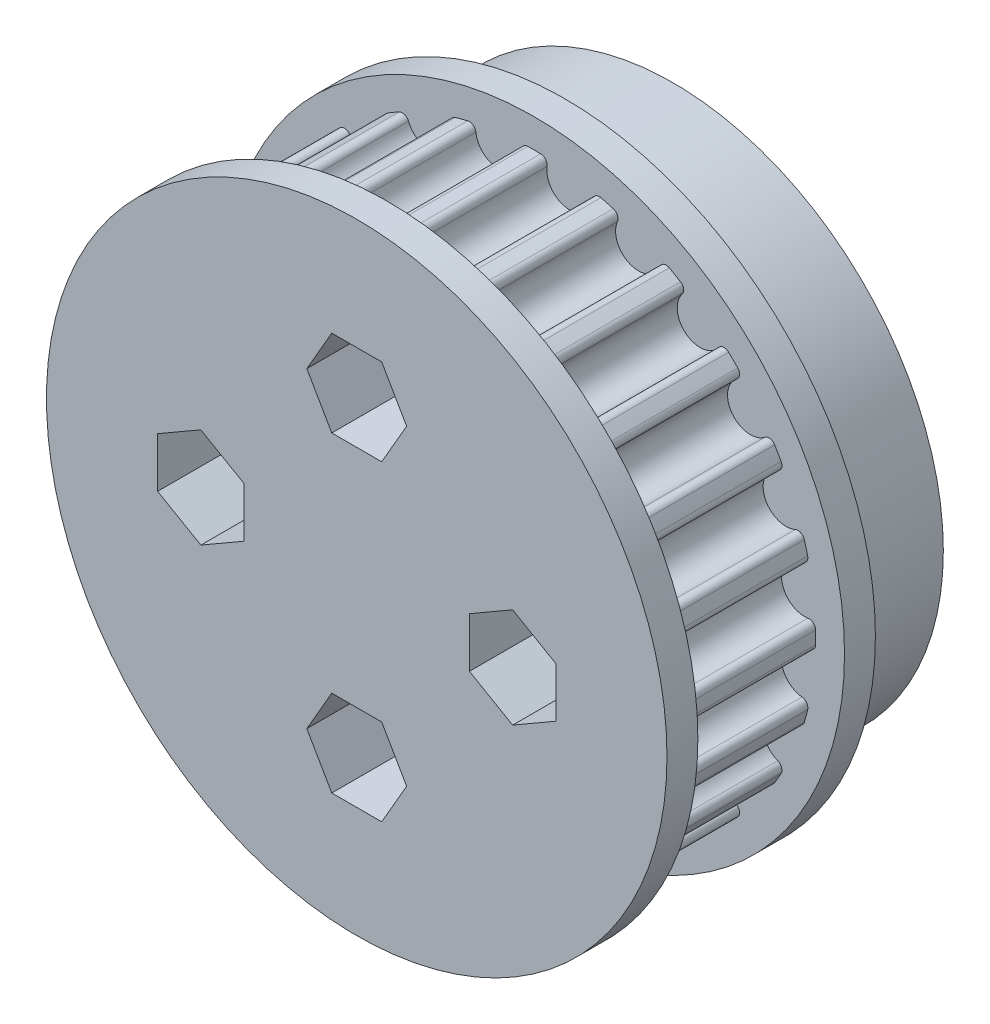
SolidWorks part; units mm, degrees
ref_plane "Front Plane" through (0, 0, 0) normal (0, 0, 1) x (1, 0, 0)
ref_plane "Top Plane" through (0, 0, 0) normal (0, 1, 0) x (1, 0, 0)
ref_plane "Right Plane" through (0, 0, 0) normal (1, 0, 0) x (0, 0, -1)
sketch "Sketch1" plane through (0, 0, 0) normal (0, 0, 1) x (1, 0, 0)
  circle A0 centre (0, 0) radius 19.0986
  dimension "D1" = 38.1972
extrude "Boss-Extrude1" add sketch "Sketch1" along normal mid plane 9.5
sketch "Sketch2" plane through (0, 0, 4.75) normal (0, 0, 1) x (1, 0, 0)
  line L0 (0, 0) -> (2.4929, 18.9352) construction
  line L1 (0, 0) -> (0, 18.2286) construction
  line L2 (0, 18.2286) -> (0, 19.0986)
  line L3 (4.7179, 17.6075) -> (4.9431, 18.4478)
  arc A0 (0, 18.2286) -> (0.4162, 18.2238) centre (0, 0) cw
  arc A1 (0.4162, 18.2238) -> (0.8316, 17.7298) centre (0.4064, 17.794) cw
  arc A2 (0.8316, 17.7298) -> (3.7856, 17.3409) centre (2.3049, 17.5075) ccw
  circle A3 centre (0, 0) radius 19.0986 construction
  arc A4 (4.7179, 17.6075) -> (4.3146, 17.7106) centre (0, 0) ccw
  arc A5 (4.3146, 17.7106) -> (3.7856, 17.3409) centre (4.2129, 17.2928) ccw
  arc A6 (4.9431, 18.4478) -> (0, 19.0986) centre (0, 0) ccw
  point P31 (2.1104, 16.0303)
  circle M1 centre (0, 0) radius 19.0986
  dimension "D1" = 1.49
  dimension "D2" = 0.43
  dimension "D3" = 0.87
  dimension "D5" = 7.5
  dimension "D4" = 2.93
extrude "Cut-Extrude1" cut sketch "Sketch2" against normal through all contours A5 A4 L3 L2 A0 A1 A2 M1 region at (2.3372, 17.7528, 4.75)
pattern_circular "CirPattern1" count 24 over 360 about axis through (0, 0, 4.75) along (0, 0, -1) of "Cut-Extrude1"
sketch "Sketch3" plane through (0, 0, 4.75) normal (0, 0, 1) x (1, 0, 0)
  circle A0 centre (0, 0) radius 20.0986
  dimension "D1" = 40.1972
extrude "Boss-Extrude2" add sketch "Sketch3" along normal blind 2
mirror "Mirror1" about plane through (0, 0, 0) normal (0, 0, 1) of "Boss-Extrude2"
sketch "Sketch5" plane through (0, 0, -6.75) normal (0, 0, 1) x (1, 0, 0)
  circle A0 centre (0, 0) radius 17.5 construction
  circle A1 centre (0, 0) radius 17.5 construction
  circle A2 centre (0, 0) radius 17.5
  dimension "D1" = 0
extrude "Boss-Extrude3" add sketch "Sketch5" against normal up to surface (7 mm away)
sketch "Sketch4" plane through (0, 0, 6.75) normal (0, 0, 1) x (1, 0, 0)
  line L0 (0, 0) -> (0, 10.0986) construction
  circle A0 centre (0, 10.0986) radius 1.6
  circle A1 centre (0, 0) radius 20.0986 construction
  circle A2 centre (10.0986, 0) radius 1.6
  circle A3 centre (0, -10.0986) radius 1.6
  circle A4 centre (-10.0986, 0) radius 1.6
  point P6 (0, 20.0986)
  point P16 (0, 0)
  dimension "D1" = 3.2
  dimension "D2" = 10
  dimension "D3" = 4
extrude "Cut-Extrude2" cut sketch "Sketch4" against normal through all
sketch "Sketch6" [suppressed] plane through (0, 0, -6.75) normal (0, 0, -1) x (-1, 0, 0)
  line L1 (9, -9) -> (-9, -9) construction
  line L2 (9, -9) -> (9, 9) construction
  line L3 (9, 9) -> (-9, 9) construction
  line L4 (-9, -9) -> (-9, 9) construction
  line L5 (9, -9) -> (-9, 9) construction
  line L6 (9, 9) -> (-9, -9) construction
  circle A0 centre (9, 9) radius 1.6
  circle A1 centre (9, -9) radius 1.6
  circle A2 centre (-9, -9) radius 1.6
  circle A3 centre (-9, 9) radius 1.6
  point P0 (0, 0)
  dimension "D1" = 3.2
  dimension "D2" = 18
extrude "Cut-Extrude3" [suppressed] cut sketch "Sketch6" against normal through all
sketch "Sketch8" plane through (0, 0, 6.75) normal (0, 0, 1) x (1, 0, 0)
  line L1 (3.2332, 10.0986) -> (1.6166, 12.8986)
  line L2 (1.6166, 12.8986) -> (-1.6166, 12.8986)
  line L3 (-1.6166, 12.8986) -> (-3.2332, 10.0986)
  line L4 (-3.2332, 10.0986) -> (-1.6166, 7.2986)
  line L5 (-1.6166, 7.2986) -> (1.6166, 7.2986)
  line L6 (1.6166, 7.2986) -> (3.2332, 10.0986)
  line L7 (12.8986, -1.6166) -> (12.8986, 1.6166)
  line L8 (12.8986, 1.6166) -> (10.0986, 3.2332)
  line L9 (10.0986, 3.2332) -> (7.2986, 1.6166)
  line L10 (7.2986, 1.6166) -> (7.2986, -1.6166)
  line L11 (7.2986, -1.6166) -> (10.0986, -3.2332)
  line L12 (10.0986, -3.2332) -> (12.8986, -1.6166)
  line L13 (3.2332, -10.0986) -> (1.6166, -7.2986)
  line L14 (1.6166, -7.2986) -> (-1.6166, -7.2986)
  line L15 (-1.6166, -7.2986) -> (-3.2332, -10.0986)
  line L16 (-3.2332, -10.0986) -> (-1.6166, -12.8986)
  line L17 (-1.6166, -12.8986) -> (1.6166, -12.8986)
  line L18 (1.6166, -12.8986) -> (3.2332, -10.0986)
  line L19 (-7.2986, -1.6166) -> (-7.2986, 1.6166)
  line L20 (-7.2986, 1.6166) -> (-10.0986, 3.2332)
  line L21 (-10.0986, 3.2332) -> (-12.8986, 1.6166)
  line L22 (-12.8986, 1.6166) -> (-12.8986, -1.6166)
  line L23 (-12.8986, -1.6166) -> (-10.0986, -3.2332)
  line L24 (-10.0986, -3.2332) -> (-7.2986, -1.6166)
  circle A0 centre (0, 10.0986) radius 2.8 construction
  circle A1 centre (10.0986, 0) radius 2.8 construction
  circle A2 centre (0, -10.0986) radius 2.8 construction
  circle A3 centre (-10.0986, 0) radius 2.8 construction
  dimension "D1" = 5.6
extrude "Cut-Extrude4" cut sketch "Sketch8" against normal blind 6
equation "\"D1@Sketch1\"=\"Driver PD\""
equation "\"D1@Boss-Extrude1\"=\"Belt Width@Leg-1.Assembly\""
equation "\"D3@Sketch2\"=(3.8-2.06)/2"
equation "\"D5@Sketch2\"=180/\"Driver Teeth\""
equation "\"D4@Sketch2\"=\"D3@Sketch2\"+2.06"
equation "\"D1@CirPattern1\"=\"Driver Teeth\""
equation "\"D1@Sketch3\"=\"Driver PD\"+2"
equation "\"D1@Boss-Extrude2\"=\"Flange Width@Leg-1.Assembly\""
equation "\"Pulley Pitch\"= 5mm"
equation "\"Driver Teeth\"= 24"
equation "\"Driver PD\"= \"Pulley Pitch\" * \"Driver Teeth\" / pi"
equation "\"Belt Width\"= 9.50mm"
equation "\"Flange Width\"= 2mm"
